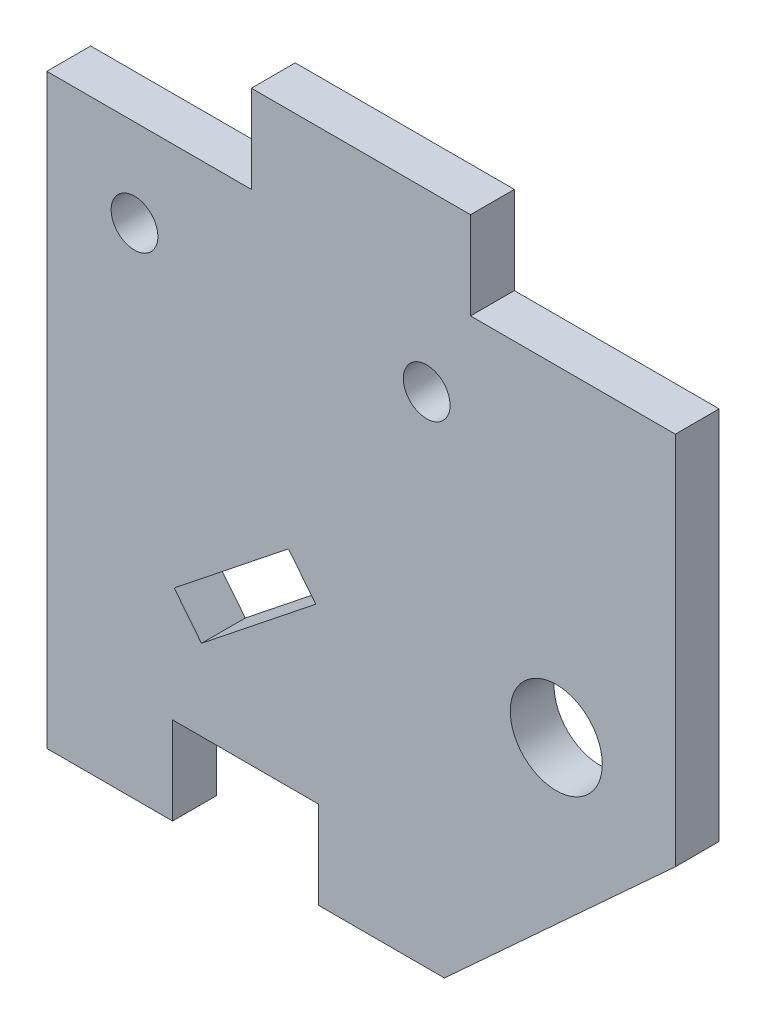
SolidWorks part; units mm, degrees
ref_plane "Plano frontal" through (0, 0, 0) normal (0, 0, 1) x (1, 0, 0)
ref_plane "Plano superior" through (0, 0, 0) normal (0, 1, 0) x (1, 0, 0)
ref_plane "Plano direito" through (0, 0, 0) normal (1, 0, 0) x (0, 0, -1)
sketch "Esboço1" plane through (0, 0, 0) normal (0, 0, 1) x (1, 0, 0)
  line L5 (0, 0) -> (43.0184, 0)
  line L10 (25.0869, -24.1416) -> (28.9434, -42.2853) construction
  line L11 (28.9434, -42.2853) -> (34.0298, -41.2041) construction
  line L12 (34.0298, -41.2041) -> (34.8684, -22.0625) construction
  line L13 (34.8684, -22.0625) -> (25.0869, -24.1416) construction
  line L14 (43.0184, 0) -> (43.0184, -40.1416)
  line L15 (43.0184, -40.1416) -> (0, -40.1416)
  line L16 (0, -40.1416) -> (0, 0)
  line L17 (21.5092, 0) -> (21.5092, -40.1416) construction
  line L18 (34.8684, -22.0625) -> (28.9434, -42.2853) construction
  line L19 (34.8684, -22.0625) -> (27.7973, -29.1335) construction
  line L20 (27.7973, -29.1335) -> (40.9134, -42.2497) construction
  line L21 (40.9134, -42.2497) -> (44.5904, -38.5727) construction
  line L22 (43.0184, -25.6466) -> (27.2125, -40.1416)
  line L25 (6, -6) -> (26, -6) construction
  line L27 (6, -6) -> (40.9134, -42.2497) construction
  line L28 (6, -6) -> (34.0298, -41.2041) construction
  line L29 (10.5845, -28.6149) -> (8.7158, -26.268)
  line L30 (18.6062, -34.1416) -> (27.2125, -34.1416) construction
  line L31 (29, 6) -> (14, 6)
  line L32 (29, 6) -> (29, 0)
  line L33 (18.6062, -40.1416) -> (18.6062, -34.1416)
  line L34 (29, 0) -> (14, 0)
  line L35 (14, 6) -> (14, 0)
  line L36 (29, 6) -> (14, 0) construction
  line L37 (29, 0) -> (14, 6) construction
  line L38 (8.7158, -26.268) -> (16.5389, -20.0391)
  line L39 (18.6062, -34.1416) -> (8.6062, -34.1416)
  line L40 (8.6062, -34.1416) -> (8.6062, -40.1416)
  line L41 (8.6062, -37.1416) -> (18.6062, -37.1416) construction
  line L42 (0, -42.2853) -> (27.2125, -42.2853) construction
  line L43 (34.8684, -22.0625) -> (27.9179, -28.7567) construction
  line L44 (16.5389, -20.0391) -> (18.4076, -22.3861)
  line L45 (18.4076, -22.3861) -> (10.5845, -28.6149)
  line L46 (18.4076, -22.3861) -> (24.275, -17.7144) construction
  line L47 (10.5845, -28.6149) -> (4.7171, -33.2866) construction
  circle A0 centre (34.8684, -22.0625) radius 3.15
  circle A1 centre (34.8684, -22.0625) radius 8.15 construction
  circle A3 centre (26, -6) radius 1.6
  circle A4 centre (6, -6) radius 1.6
  circle A15 centre (26, -6) radius 3 construction
  circle A16 centre (34.8684, -22.0625) radius 10 construction
  point P5 (43.0184, -22.0625)
  point P11 (32.5996, -24.2477)
  point P12 (20.0979, -34.1416)
  point P25 (38.0184, -22.0625)
  point P31 (21.5, 3)
  point P33 (12.5402, -27.0577)
  point P50 (13.6062, -37.1416)
  point P55 (13.6062, -42.2853)
  dimension "D3" = 6.3
  dimension "D6" = 10
  dimension "D11" = 6.5
  dimension "D19" = 45
  dimension "D18" = 6
  dimension "D10" = 10
  dimension "D21" = 6
  dimension "D23" = 20
  dimension "D15" = 10
  dimension "D13" = 3.2
  dimension "D4" = 19.16
  dimension "D5" = 5.2
  dimension "D7" = 12
  dimension "D8" = 10
  dimension "D9" = 5
  dimension "D12" = 45
  dimension "D14" = 6.5
  dimension "D16" = 6
  dimension "D17" = 20
  dimension "D20" = 3
  dimension "D22" = 25
  dimension "D24" = 6
  dimension "D25" = 15
  dimension "D26" = 6
  dimension "D27" = 15
  dimension "D28" = 14
  dimension "D29" = 8
extrude "Ressalto-extrusão1" add sketch "Esboço1" along normal blind 3 contours A1 L5 L16 A4 A3 | L5 A1 | L31 L35 L5 L32 | L32 L31 L35 L34 region at (20.5088, -18.2177, 0) region at (21.5, 3, 0)
